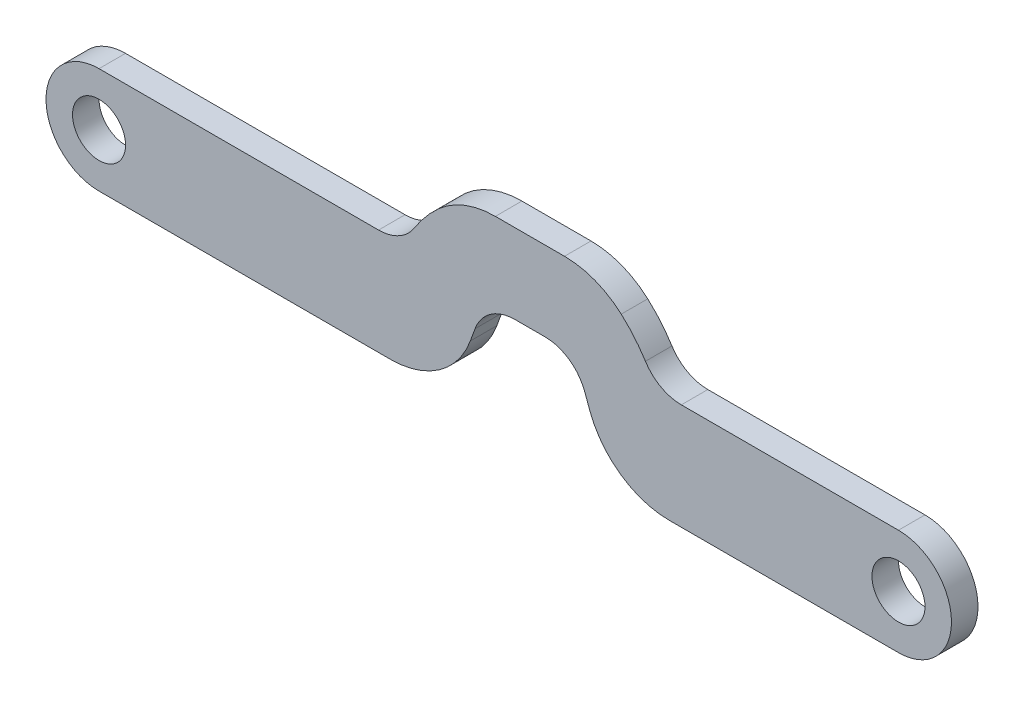
SolidWorks part; units mm, degrees
ref_plane "Спереди" through (0, 0, 0) normal (0, 0, 1) x (1, 0, 0)
ref_plane "Сверху" through (0, 0, 0) normal (0, 1, 0) x (1, 0, 0)
ref_plane "Справа" through (0, 0, 0) normal (1, 0, 0) x (0, 0, -1)
sketch "Эскиз1" plane through (0, 0, 0) normal (0, 0, 1) x (1, 0, 0)
  line L0 (0, 0) -> (-30.1536, 0)
  line L1 (-30.1536, -2) -> (0, -2)
  line L2 (-30.1536, 2) -> (0, 2)
  circle A0 centre (-30.1536, 0) radius 1
  circle A1 centre (0, 0) radius 1
  circle A2 centre (-30.1536, 0) radius 2
  circle A3 centre (0, 0) radius 2
  dimension "D1" = 30.1536
extrude "Бобышка-Вытянуть1" add sketch "Эскиз1" along normal mid plane 1 contours A3 L2 A2 L0 | A3 L0 A2 L1 | A2 A0 | A3 A1 region at (-15.0768, 1.0176, 0) region at (-28.7794, -1.3742, 0) region at (-15.0768, -1.0176, 0) region at (-1.3742, 1.3742, 0)
sketch "Sketch1" plane through (0, 0, 0) normal (0, 0, 1) x (1, 0, 0)
  line L0 (0, 0) -> (-14, 0)
  line L1 (-14, 0) -> (-14, 1.5)
  line L2 (-25.5979, -2) -> (-2.0642, -2)
  line L3 (-14, 0) -> (-30.1536, 0)
  line L7 (-14, 1.5) -> (-20.4712, -4.9712)
  line L11 (0, 2) -> (-30.8022, 2)
  line L12 (-14, 1.5) -> (-7.5288, -4.9712)
  line L13 (-20.4712, -4.9712) -> (-7.5288, -4.9712)
  line L14 (-15.6569, 5.5) -> (-30.1281, -8.9712)
  line L15 (-30.1281, -8.9712) -> (2.1281, -8.9712)
  line L16 (-12.3431, 5.5) -> (2.1281, -8.9712)
  line L17 (-14, 1.5) -> (-14, 5.5)
  line L18 (-14, 5.5) -> (-15.6569, 5.5)
  line L19 (-14, 5.5) -> (-12.3431, 5.5)
  line L21 (-14, 7.1569) -> (-30.1281, -8.9712) construction
  line L22 (-14, 7.1569) -> (2.1281, -8.9712) construction
  point P6 (-9.7278, -2.9956)
  point P9 (-14.7071, 0.7071)
  point P10 (-13.2929, 0.7071)
  point P11 (-21.4142, -2.5858)
  point P15 (-16, 0)
  point P22 (-10, 0)
  dimension "D1" = 4
  dimension "D4" = 14
  dimension "D2" = 1.5
sketch "Sketch2" plane through (0, 0, 0) normal (0, 0, 1) x (1, 0, 0)
  line L0 (0, 0) -> (-13.9, 0)
  line L1 (-13.9, -2) -> (-8.7079, -2)
  line L2 (-15.9203, 0.7353) -> (-16.9159, -2)
  line L3 (-11.8797, 0.7353) -> (-10.8841, -2)
  line L4 (-13.9, 0) -> (-13.9, -2)
  line L5 (-13.9, -2) -> (-19.127, -2)
  line L6 (-18.7394, 1.7614) -> (-19.735, -0.9739)
  line L7 (-9.0606, 1.7614) -> (-8.065, -0.9739)
  line L8 (-13.9, 5.15) -> (-13.9, 4.65)
  line L9 (-13.9, 4.65) -> (-17.7533, 4.65)
  line L10 (-13.9, 4.65) -> (-9.692, 4.65)
  line L11 (-13.9, 2.15) -> (-13.9, 1.65)
  line L12 (-13.9, 1.65) -> (-16.1112, 1.65)
  line L13 (-13.9, 1.65) -> (-11.2512, 1.65)
  circle A0 centre (-13.9, 0) radius 2.15
  circle A1 centre (-13.9, 0) radius 5.15
  dimension "D1" = 4.3
extrude "Extrude1" add sketch "Sketch2" along normal mid plane 1 contours L0 A1 L5 L2 A0 L3 | L1 A1 L0 L3 | L11 A0 L12 | L13 A0 L11 | L8 A1 L9 | L10 A1 L8 region at (-11.6306, 0.4096, 0) region at (-10.0716, -0.9205, 0) region at (-13.374, 1.8521, 0) region at (-14.426, 1.8521, 0) region at (-13.0643, 4.8509, 0) region at (-14.7357, 4.8509, 0)
extrude "Extrude2" cut sketch "Sketch" against normal mid plane 1 contours A0 L2 L5 | A0 L1 L3 L0 | L1 A0 L0 L4 | L0 A0 L5 L4 | A0 L0 L3 | L8 A1 L9 | L10 A1 L8 region at (-12.9737, -0.8868, 0) region at (-11.7214, 0.1861, 0) region at (-14.2333, 0.1753, 0) region at (-11.7391, -1.3677, 0) region at (-16.0613, -1.3378, 0) region at (-13.0643, 4.8509, 0) region at (-14.7357, 4.8509, 0)
sketch "Sketch" plane through (0, 0, 0) normal (0, 0, 1) x (1, 0, 0) same geometry as "Sketch2"
fillet "Fillet1" radius 1.6 4 edges at (-9.1542, 2, 0) (-18.6458, 2, 0) (-12.5216, 1.65, 0) (-15.2784, 1.65, 0)
fillet "Fillet2" radius 3.2 4 edges at (-10.8841, -2, 0) (-16.9159, -2, 0) (-11.6864, 4.65, 0) (-16.1136, 4.65, 0)
